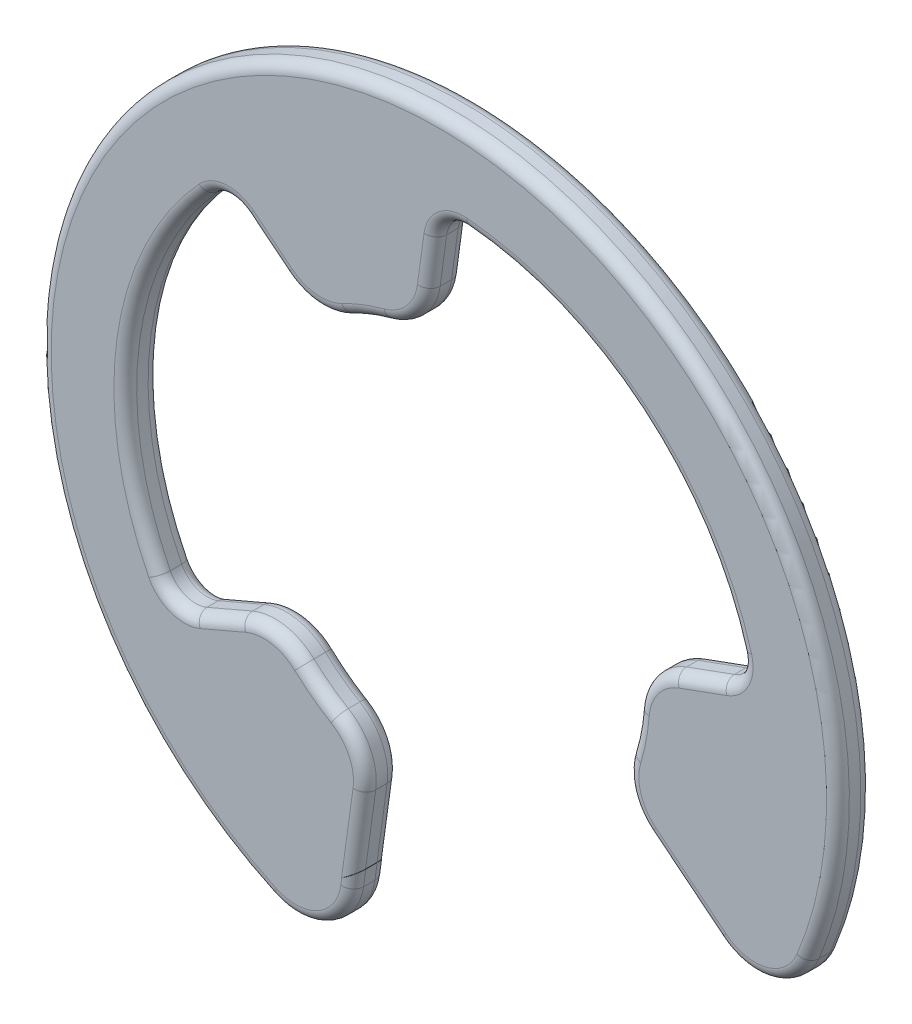
SolidWorks part; units mm, degrees
ref_plane "Front Plane" through (0, 0, 0) normal (0, 0, 1) x (1, 0, 0)
ref_plane "Top Plane" through (0, 0, 0) normal (0, 1, 0) x (1, 0, 0)
ref_plane "Right Plane" through (0, 0, 0) normal (1, 0, 0) x (0, 0, -1)
sketch "Sketch1" plane through (0, 0, 0) normal (0, 0, 1) x (1, 0, 0)
  line L3 (-4.2668, -2.7121) -> (-3.4664, -2.3689)
  line L4 (-1.4849, -5.2958) -> (-1.3071, -4.0056)
  line L5 (3.679, -2.0811) -> (4.68, -2.8893)
  line L6 (4.1438, 0.5878) -> (4.9818, 0.8932)
  line L7 (-0.0619, 5.0492) -> (-0.1772, 4.2098)
  line L8 (-3.3762, 3.7633) -> (-2.6982, 3.2168)
  line L9 (-1.4817, -5.2967) -> (-1.5208, -5.5839)
  line L10 (3.679, -2.0811) -> (4.9136, -3.0778)
  arc A0 (6.4654, -2.6831) -> (-2.9302, -6.3572) centre (0, 0) ccw
  arc A1 (-4.059, 3.7115) -> (-4.9102, -2.4778) centre (0, 0) ccw
  arc A2 (-2.3896, -2.5573) -> (-1.7872, -3.0093) centre (0, 0) ccw
  arc A3 (-0.9083, 3.3801) -> (-1.6104, 3.1075) centre (0, 0) ccw
  arc A4 (3.3501, -1.0135) -> (3.4893, -0.2736) centre (0, 0) ccw
  arc A5 (-1.4849, -5.2958) -> (-1.4817, -5.2967) centre (0, 0) ccw
  arc A6 (5.2917, 1.4992) -> (0.4768, 5.4793) centre (0, 0) ccw
  arc A7 (4.9136, -3.0778) -> (6.4654, -2.6831) centre (5.5417, -2.2998) ccw
  arc A8 (-1.5208, -5.5839) -> (-2.9302, -6.3572) centre (-2.5116, -5.449) cw
  arc A9 (3.679, -2.0811) -> (3.3501, -1.0135) centre (4.3072, -1.303) cw
  arc A10 (-1.3071, -4.0056) -> (-1.7872, -3.0093) centre (-2.2978, -3.8691) ccw
  arc A11 (-3.4664, -2.3689) -> (-2.3896, -2.5573) centre (-3.0723, -3.288) cw
  arc A12 (-0.1772, 4.2098) -> (-0.9083, 3.3801) centre (-1.1679, 4.3458) cw
  arc A13 (-2.6982, 3.2168) -> (-1.6104, 3.1075) centre (-2.0706, 3.9953) ccw
  arc A14 (4.1438, 0.5878) -> (3.4893, -0.2736) centre (4.4862, -0.3518) ccw
  arc A15 (-4.2668, -2.7121) -> (-4.9102, -2.4778) centre (-4.4639, -2.2526) cw
  arc A16 (4.9818, 0.8932) -> (5.2917, 1.4992) centre (4.8107, 1.363) ccw
  arc A17 (-0.0619, 5.0492) -> (0.4768, 5.4793) centre (0.4335, 4.9812) cw
  arc A18 (-3.3762, 3.7633) -> (-4.059, 3.7115) centre (-3.69, 3.3741) ccw
  dimension "D1" = 14
  dimension "D2" = 1.5
  dimension "D8" = 7
  dimension "D18" = 1
  dimension "D3" = 1
  dimension "D4" = 1
  dimension "D5" = 0.5
extrude "Boss-Extrude1" add sketch "Sketch1" along normal blind 0.6 contours A9 A4 A14 L6 A16 A6 A17 L7 A12 A3 A13 L8 A18 A1 A15 L3 A11 A2 A10 L4 A5 L9 A8 A0 A7 L10
fillet "Fillet1" radius 0.2 52 edges at (5.7883, -3.2689, 0) (-2.5493, 6.5193, 0) (-2.0306, -6.3257, 0) (-1.5012, -5.4403, 0) (-1.4833, -5.2962, 0) (-1.396, -4.6507, 0) (-1.3969, -3.4351, 0) (-2.1006, -2.7996, 0) (-2.9, -2.3029, 0) (-3.8666, -2.5405, 0) (-4.6349, -2.7224, 0) (-5.4487, 0.7494, 0) (-3.7278, 3.8726, 0) (-3.0372, 3.4901, 0) (-2.1706, 3.0003, 0) (-1.2667, 3.2627, 0) (-0.4176, 3.6847, 0) (-0.1195, 4.6295, 0) (0.1215, 5.3719, 0) (3.5042, 4.2392, 0) (5.2558, 1.1353, 0) (4.5628, 0.7405, 0) (3.69, 0.2533, 0) (3.4396, -0.6473, 0) (3.3516, -1.5975, 0) (4.2963, -2.5795, 0) (3.3516, -1.5975, 0.6) (3.4396, -0.6473, 0.6) (3.69, 0.2533, 0.6) (4.5628, 0.7405, 0.6) (5.2558, 1.1353, 0.6) (3.5042, 4.2392, 0.6) (0.1215, 5.3719, 0.6) (-0.1195, 4.6295, 0.6) (-0.4176, 3.6847, 0.6) (-1.2667, 3.2627, 0.6) (-2.1706, 3.0003, 0.6) (-3.0372, 3.4901, 0.6) (-3.7278, 3.8726, 0.6) (-5.4487, 0.7494, 0.6) (-4.6349, -2.7224, 0.6) (-3.8666, -2.5405, 0.6) (-2.9, -2.3029, 0.6) (-2.1006, -2.7996, 0.6) (-1.3969, -3.4351, 0.6) (-1.396, -4.6507, 0.6) (-1.4833, -5.2962, 0.6) (-1.5012, -5.4403, 0.6) (-2.0306, -6.3257, 0.6) (-2.5493, 6.5193, 0.6) (5.7883, -3.2689, 0.6) (4.2963, -2.5795, 0.6)
